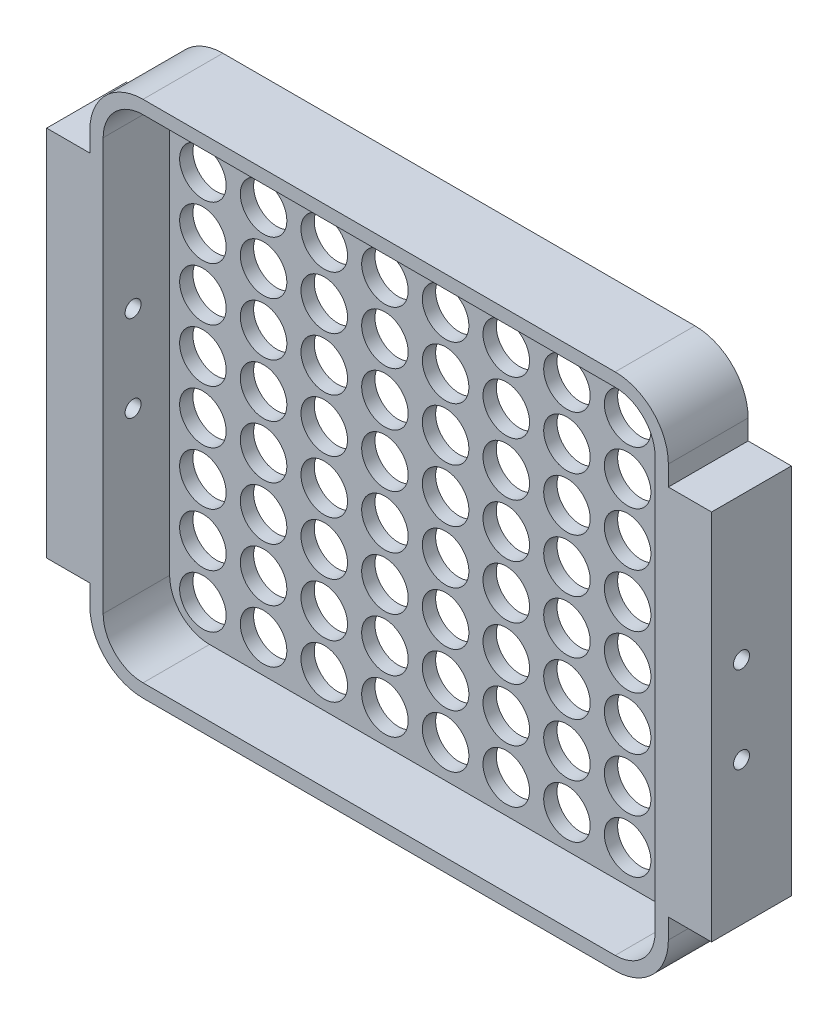
SolidWorks part; units mm, degrees
note: The reader was unsure of these and kept them because the rebuilt part matched: shared geometry of "Sketch15<2>".
ref_plane "Front Plane" through (0, 0, 0) normal (0, 0, 1) x (1, 0, 0)
ref_plane "Top Plane" through (0, 0, 0) normal (0, 1, 0) x (1, 0, 0)
ref_plane "Right Plane" through (0, 0, 0) normal (1, 0, 0) x (0, 0, -1)
sketch "Sketch1" plane through (0, 0, 0) normal (0, 0, 1) x (1, 0, 0)
  line L1 (-35.5, 37) -> (35.5, 37)
  line L2 (-41.5, 31) -> (-41.5, -31)
  line L3 (-35.5, -37) -> (35.5, -37)
  line L4 (41.5, 31) -> (41.5, -31)
  line L5 (-41.5, 37) -> (41.5, -37) construction
  line L6 (-41.5, -37) -> (41.5, 37) construction
  arc A0 (35.5, 37) -> (41.5, 31) centre (35.5, 31) cw
  arc A1 (35.5, -37) -> (41.5, -31) centre (35.5, -31) ccw
  arc A2 (-41.5, -31) -> (-35.5, -37) centre (-35.5, -31) ccw
  arc A3 (-35.5, 37) -> (-41.5, 31) centre (-35.5, 31) ccw
  point P0 (0, 0)
  dimension "D3" = 6
  dimension "D1" = 74
  dimension "D2" = 83
extrude "Extrude-Thin1" add sketch "Sketch1" along normal blind 10 thin thin type one direction wall 2
sketch "Sketch2" plane through (0, 0, 0) normal (0, 0, -1) x (-1, 0, 0)
  line L1 (-35.5, 37) -> (35.5, 37)
  line L2 (-41.5, 31) -> (-41.5, -31)
  line L3 (-35.5, -37) -> (35.5, -37)
  line L4 (41.5, 31) -> (41.5, -31)
  line L5 (-41.5, 37) -> (41.5, -37) construction
  line L6 (-41.5, -37) -> (41.5, 37) construction
  line L8 (-35.5, 37) -> (35.5, 37) construction
  line L9 (-41.5, -31) -> (-41.5, 31) construction
  line L10 (-43.5, 31) -> (-43.5, -31)
  line L11 (-35.5, -39) -> (35.5, -39)
  line L12 (43.5, -31) -> (43.5, 31)
  line L13 (-35.5, 39) -> (35.5, 39)
  arc A0 (35.5, 37) -> (41.5, 31) centre (35.5, 31) cw
  arc A1 (35.5, -37) -> (41.5, -31) centre (35.5, -31) ccw
  arc A2 (-41.5, -31) -> (-35.5, -37) centre (-35.5, -31) ccw
  arc A3 (-35.5, 37) -> (-41.5, 31) centre (-35.5, 31) ccw
  arc A4 (-43.5, -31) -> (-35.5, -39) centre (-35.5, -31) ccw
  arc A5 (35.5, -39) -> (43.5, -31) centre (35.5, -31) ccw
  arc A6 (43.5, 31) -> (35.5, 39) centre (35.5, 31) ccw
  arc A7 (-43.5, 31) -> (-35.5, 39) centre (-35.5, 31) cw
  point P0 (0, 0)
  arc M9 (-35.5, 39) -> (-43.5, 31) centre (-35.5, 31) ccw
  line M10 (-43.5, 31) -> (-43.5, -31)
  arc M11 (-43.5, -31) -> (-35.5, -39) centre (-35.5, -31) ccw
  line M12 (-35.5, -39) -> (35.5, -39)
  arc M13 (35.5, -39) -> (43.5, -31) centre (35.5, -31) ccw
  line M14 (43.5, -31) -> (43.5, 31)
  arc M15 (43.5, 31) -> (35.5, 39) centre (35.5, 31) ccw
  line M16 (35.5, 39) -> (-35.5, 39)
  line M17 (-41.5, -31) -> (-41.5, 31)
  arc M18 (-41.5, 31) -> (-35.5, 37) centre (-35.5, 31) cw
  line M19 (-35.5, 37) -> (35.5, 37)
  arc M20 (35.5, 37) -> (41.5, 31) centre (35.5, 31) cw
  line M21 (41.5, 31) -> (41.5, -31)
  arc M22 (41.5, -31) -> (35.5, -37) centre (35.5, -31) cw
  line M23 (35.5, -37) -> (-35.5, -37)
  arc M24 (-35.5, -37) -> (-41.5, -31) centre (-35.5, -31) cw
  dimension "D1" = 6
extrude "Boss-Extrude1" add sketch "Sketch2" along normal blind 2 contours M17 M24 M23 M22 M21 M20 M19 M18 | M16 M9 M10 M11 M12 M13 M14 M15 M24 M17 M18 M19 M20 M21 M22 M23
sketch "Sketch3" plane through (-43.5, 0, 0) normal (-1, 0, 0) x (0, 0, 1)
  line L0 (-2, -31) -> (-2, 31) construction
  line L1 (-2, 28) -> (1, 28)
  line L2 (-2, 28) -> (-2, -28)
  line L3 (-2, -28) -> (1, -28)
  line L4 (1, 28) -> (1, -28)
  line L5 (10, 31) -> (-2, 31) construction
  line L6 (10, -31) -> (-2, -31) construction
  dimension "D1" = 3
  dimension "D2" = 3
  dimension "D3" = 3
extrude "Boss-Extrude2" add sketch "Sketch3" along normal blind 6.5
sketch "Sketch4" plane through (-50, 0, 0) normal (-1, 0, 0) x (0, 0, 1)
  line L0 (1, 28) -> (-2, 28) construction
  line L1 (1, -28) -> (10, -28)
  line L2 (1, -28) -> (1, 28)
  line L3 (1, 28) -> (10, 28)
  line L4 (10, -28) -> (10, 28)
  dimension "D1" = 9
extrude "Boss-Extrude3" add sketch "Sketch4" against normal blind 5
sketch "Sketch5" plane through (-50, 0, 0) normal (-1, 0, 0) x (0, 0, 1)
  line L0 (1, 28) -> (1, -28) construction
  line L1 (10, 28) -> (-2, 28) construction
  line L2 (-2, -28) -> (10, -28) construction
  line L3 (1, 28) -> (1, -28) construction
  line L4 (1, 0) -> (10, 0) construction
  line L5 (10, -28) -> (10, 28) construction
  line L6 (5.5, 28) -> (5.5, -28) construction
  point P12 (5.5, -6.5)
  point P15 (5.5, 0)
  point P16 (5.5, 6.5)
  point P17 (5.5, -6.5)
  point P18 (5.5, 6.5)
  dimension "D1" = 6.5
hole_wizard "Ø3.0mm Dowel Hole1" positions "3DSketch1" profile "Sketch6" hole size "Ø3.0" standard "ANSI Metric"
sketch3d "3DSketch1"
  point P0 (-50, -6.5, 5.5)
  point P3 (-50, 6.5, 5.5)
sketch "Sketch6" plane through (-50, -6.5, 5.5) normal (0, 1, 0) x (0, 0, 1)
  line L0 (0, 0) -> (0, 150)
  line L1 (0, 150) -> (1.5, 150)
  line L2 (1.5, 150) -> (1.5, 0)
  line L5 (1.5, 0) -> (0, 0)
  line L10 (0, 150) -> (-1.5, 150) construction
  line L11 (0, -6.35) -> (0, 107.95) construction
  dimension "Hole Dia." = 3
  dimension "Hole Depth" = 150
  dimension "Drill Angle" = 180
fillet "Fillet1" [suppressed] radius 3
fillet "Fillet2" [suppressed] radius 1
mirror "Mirror2" about plane through (0, 0, 0) normal (1, 0, 0) of "Fillet2", "Fillet1", "Boss-Extrude3", "Boss-Extrude2"
sketch "Sketch7" [suppressed] plane through (50, 0, 0) normal (1, 0, 0) x (0, 0, -1)
  point P0 (-5.5, -6.5)
  point P1 (-5.5, 6.5)
hole_wizard "Ø3.0mm Dowel Hole2" [suppressed] positions "Sketch8" profile "Sketch9" hole size "Ø3.0" standard "ANSI Metric"
sketch "Sketch8" [suppressed] plane through (50, 0, 0) normal (1, 0, 0) x (0, 0, -1)
  point P0 (-5.5, -6.5)
  point P3 (-5.5, 6.5)
sketch "Sketch9" plane through (50, -6.5, 5.5) normal (0, 1, 0) x (0, 0, -1)
  line L0 (0, 0) -> (0, 4.999)
  line L1 (0, 4.999) -> (1.5, 4.999)
  line L2 (1.5, 4.999) -> (1.5, 0)
  line L5 (1.5, 0) -> (0, 0)
  line L10 (0, 4.999) -> (-1.5, 4.999) construction
  line L11 (0, -6.35) -> (0, 107.95) construction
  dimension "Hole Dia." = 3
  dimension "Hole Depth" = 4.999
  dimension "Drill Angle" = 180
fillet "Fillet3" [suppressed] radius 3
sketch "Sketch10" plane through (0, 0, 0) normal (0, 0, 1) x (1, 0, 0)
  line L0 (0, 37) -> (0, -37) construction
  line L1 (36.5, 37) -> (36.5, -37) construction
  line L2 (35.5, 37) -> (-35.5, 37) construction
  line L31 (-41.5, -32) -> (41.5, -32) construction
  line L34 (35.5, 37) -> (-35.5, 37) construction
  line L35 (41.5, -31) -> (41.5, 31) construction
  line L36 (-35.5, -37) -> (35.5, -37) construction
  line L37 (-35.5, -37) -> (35.5, -37) construction
  line L38 (-41.5, 0) -> (41.5, 0) construction
  line L39 (-41.5, 31) -> (-41.5, -31) construction
  line L40 (41.5, -31) -> (41.5, 31) construction
  line L41 (-36.5, 37) -> (-36.5, 32) construction
  line L42 (-36.5, 32) -> (-41.5, 32) construction
  line L43 (-41.5, 31) -> (-41.5, -31) construction
  circle A1 centre (-27.375, 32) radius 3.5
  circle A2 centre (-18.25, 32) radius 3.5
  circle A5 centre (-9.125, 32) radius 3.5
  circle A6 centre (0, 32) radius 3.5
  circle A7 centre (-36.5, 32) radius 3.5
  circle A8 centre (9.125, 32) radius 3.5
  circle A9 centre (-27.375, 24) radius 3.5
  circle A10 centre (-18.25, 24) radius 3.5
  circle A11 centre (-9.125, 24) radius 3.5
  circle A12 centre (0, 24) radius 3.5
  circle A13 centre (9.125, 24) radius 3.5
  circle A14 centre (-27.375, 16) radius 3.5
  circle A15 centre (-18.25, 16) radius 3.5
  circle A16 centre (-9.125, 16) radius 3.5
  circle A17 centre (0, 16) radius 3.5
  circle A18 centre (9.125, 16) radius 3.5
  circle A19 centre (-27.375, 8) radius 3.5
  circle A20 centre (-18.25, 8) radius 3.5
  circle A21 centre (-9.125, 8) radius 3.5
  circle A22 centre (0, 8) radius 3.5
  circle A23 centre (9.125, 8) radius 3.5
  circle A24 centre (-27.375, 0) radius 3.5
  circle A25 centre (-18.25, 0) radius 3.5
  circle A26 centre (-9.125, 0) radius 3.5
  circle A27 centre (0, 0) radius 3.5
  circle A28 centre (9.125, 0) radius 3.5
  circle A29 centre (-36.5, 24) radius 3.5
  circle A30 centre (-36.5, 16) radius 3.5
  circle A31 centre (-36.5, 8) radius 3.5
  circle A32 centre (-36.5, 0) radius 3.5
  circle A33 centre (-36.5, -8) radius 3.5
  circle A34 centre (-27.375, -8) radius 3.5
  circle A35 centre (-18.25, -8) radius 3.5
  circle A36 centre (-9.125, -8) radius 3.5
  circle A37 centre (0, -8) radius 3.5
  circle A38 centre (9.125, -8) radius 3.5
  circle A39 centre (-36.5, -16) radius 3.5
  circle A40 centre (-27.375, -16) radius 3.5
  circle A41 centre (-18.25, -16) radius 3.5
  circle A42 centre (-9.125, -16) radius 3.5
  circle A43 centre (0, -16) radius 3.5
  circle A44 centre (9.125, -16) radius 3.5
  circle A45 centre (-36.5, -24) radius 3.5
  circle A46 centre (-27.375, -24) radius 3.5
  circle A47 centre (-18.25, -24) radius 3.5
  circle A48 centre (-9.125, -24) radius 3.5
  circle A49 centre (0, -24) radius 3.5
  circle A50 centre (9.125, -24) radius 3.5
  circle A51 centre (-36.5, -32) radius 3.5
  circle A52 centre (-27.375, -32) radius 3.5
  circle A53 centre (-18.25, -32) radius 3.5
  circle A54 centre (-9.125, -32) radius 3.5
  circle A55 centre (0, -32) radius 3.5
  circle A56 centre (9.125, -32) radius 3.5
  circle A57 centre (18.25, 32) radius 3.5
  circle A58 centre (27.375, 32) radius 3.5
  circle A59 centre (36.5, 32) radius 3.5
  circle A60 centre (18.25, 24) radius 3.5
  circle A61 centre (27.375, 24) radius 3.5
  circle A62 centre (36.5, 24) radius 3.5
  circle A63 centre (18.25, 16) radius 3.5
  circle A64 centre (27.375, 16) radius 3.5
  circle A65 centre (36.5, 16) radius 3.5
  circle A66 centre (18.25, 8) radius 3.5
  circle A67 centre (27.375, 8) radius 3.5
  circle A68 centre (36.5, 8) radius 3.5
  circle A69 centre (18.25, 0) radius 3.5
  circle A70 centre (27.375, 0) radius 3.5
  circle A71 centre (36.5, 0) radius 3.5
  circle A72 centre (18.25, -8) radius 3.5
  circle A73 centre (27.375, -8) radius 3.5
  circle A74 centre (36.5, -8) radius 3.5
  circle A75 centre (18.25, -16) radius 3.5
  circle A76 centre (27.375, -16) radius 3.5
  circle A77 centre (36.5, -16) radius 3.5
  circle A78 centre (18.25, -24) radius 3.5
  circle A79 centre (27.375, -24) radius 3.5
  circle A80 centre (36.5, -24) radius 3.5
  circle A81 centre (18.25, -32) radius 3.5
  circle A82 centre (27.375, -32) radius 3.5
  circle A83 centre (36.5, -32) radius 3.5
  dimension "D4" = 5
  dimension "D3" = 7
  dimension "D8" = 8
  dimension "D9" = 9.125
  dimension "D1" = 5
  dimension "D2" = 5
  dimension "D6" = 9
  dimension "D7" = 9
  dimension "D5" = 5
extrude "Cut-Extrude1" cut sketch "Sketch10" against normal through all both and the other way through all
sketch "Sketch11" plane through (0, 0, 0) normal (0, 0, 1) x (1, 0, 0)
  line L0 (-36.5, 28.5) -> (-36.5, 27.5) construction
  line L1 (-41.5, 31) -> (-41.5, -31) construction
  line L2 (-41.5, 29) -> (41.5, 29)
  line L3 (-41.5, 29) -> (-41.5, 27)
  line L4 (-41.5, 27) -> (41.5, 27)
  line L5 (41.5, 29) -> (41.5, 27)
  line L6 (41.5, -31) -> (41.5, 31) construction
  line L7 (-36.5, 28) -> (-19.5599, 28) construction
  line L8 (-36.5, 20.5) -> (-36.5, 19.5) construction
  line L9 (-36.5, 20) -> (-14.0478, 20) construction
  circle A0 centre (-36.5, 32) radius 3.5 construction
  circle A1 centre (-36.5, 24) radius 3.5 construction
  circle A2 centre (-36.5, 16) radius 3.5 construction
  dimension "D1" = 1
  dimension "D2" = 1
sketch "Sketch12" plane through (-45, 0, 0) normal (1, 0, 0) x (0, 0, -1)
  line L1 (-1, 28) -> (-10, 28)
  line L2 (-1, 28) -> (-1, -28)
  line L3 (-1, -28) -> (-10, -28)
  line L4 (-10, 28) -> (-10, -28)
  circle A0 centre (-5.5, 6.5) radius 1.5
  circle A1 centre (-5.5, -6.5) radius 1.5
extrude "Boss-Extrude4" add sketch "Sketch12" along normal up to surface (1.5 mm away)
sketch "Sketch13" plane through (45, 0, 0) normal (-1, 0, 0) x (0, 0, 1)
  line L1 (10, 28) -> (1, 28)
  line L2 (10, 28) -> (10, -28)
  line L3 (10, -28) -> (1, -28)
  line L4 (1, 28) -> (1, -28)
  circle A0 centre (5.5, 6.5) radius 1.5
  circle A1 centre (5.5, 6.5) radius 1.5 construction
  circle A2 centre (5.5, -6.5) radius 1.5
  circle A3 centre (5.5, -6.5) radius 1.5 construction
extrude "Boss-Extrude5" add sketch "Sketch13" along normal up to surface (1.5 mm away)
sketch "Sketch14" plane through (45, 0, 0) normal (-1, 0, 0) x (0, 0, 1)
  circle A0 centre (5.5, -6.5) radius 1.5
  circle A1 centre (5.5, 6.5) radius 1.5
extrude "Cut-Extrude2" cut sketch "Sketch14" against normal through all both and the other way through all
sketch "Sketch15" plane through (-50, 0, 0) normal (-1, 0, 0) x (0, 0, 1)
  circle A0 centre (5.5, 6.5) radius 1.2
  circle A1 centre (5.5, -6.5) radius 1.2
  circle A2 centre (5.5, 6.5) radius 1.5
  circle A3 centre (5.5, -6.5) radius 1.5
  dimension "D1" = 2.4
  dimension "D2" = 2.4
extrude "Boss-Extrude6" add sketch "Sketch15" against normal up to surface (8.5 mm away) up to face at (-41.5, -5, 5.5)
extrude "Boss-Extrude7" add sketch "Sketch15<2>" along normal up to surface (8.5 mm away) from surface at -100 up to face at (41.5, -6.5, 7) starting at face at (50, -6.5, 7)
sketch "Sketch15<2>" plane through (-50, 0, 0) normal (-1, 0, 0) x (0, 0, 1) same geometry as "Sketch15"
